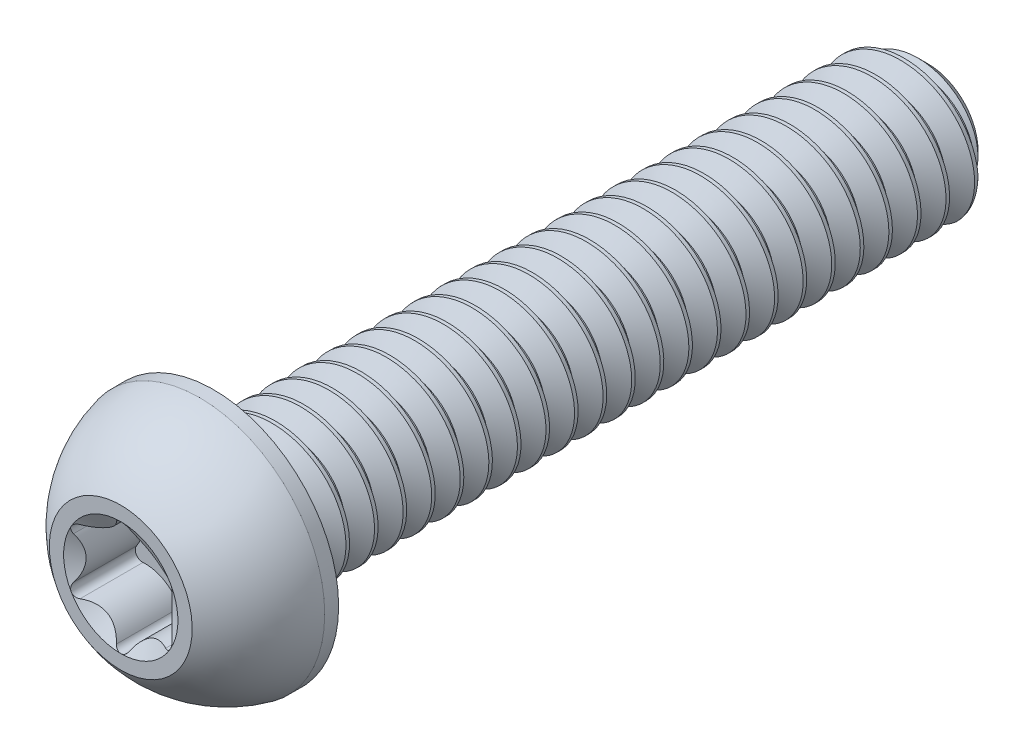
SolidWorks part; units mm, degrees
material "18-8 Stainless Steel"
ref_plane "Front" through (0, 0, 0) normal (0, 0, 1) x (1, 0, 0)
ref_plane "Top" through (0, 0, 0) normal (0, 1, 0) x (1, 0, 0)
ref_plane "Right" through (0, 0, 0) normal (1, 0, 0) x (0, 0, -1)
sketch "Sketch1" plane through (0, 0, 0) normal (1, 0, 0) x (0, 0, -1)
  line L2 (1.3, 1) -> (11.3, 1)
  line L3 (11.3, 1) -> (11.3, 0)
  line L4 (11.3, 0) -> (1.3, 0)
  line L6 (1.105, 1.75) -> (1.3, 1.75) construction
  line L7 (11.3, 1) -> (11.3, -1) construction
  line L8 (0, 0) -> (1.3, 0) construction
  line L9 (1.3, 1.75) -> (1.3, -1.75) construction
  line L11 (1.3, 1) -> (1.3, 0)
  line L14 (0, 0) -> (0, 1) construction
  arc A3 (0, 1) -> (1.105, 1.75) centre (1.4858, 0) cw construction
  dimension "D1" = 0.195
revolve "Revolve1" add sketch "Sketch1" angle 360 mid plane about L4
sketch "Sketch3" plane through (0, 0, -11.3) normal (0, 0, -1) x (-1, 0, 0)
  circle A0 centre (0, 0) radius 1
curve "Helix/Spiral1" pitch 0.4 height 10.4 radius 1 centre (0, 0, -11.3) axis (0, 0, 1) start towards (0, 1, 0)
sketch "Sketch2" plane through (0, 0, 0) normal (1, 0, 0) x (0, 0, -1)
  line L0 (11.3, 1) -> (11.65, 1) construction
  line L1 (11.65, 1) -> (11.5, 0.7402)
  line L2 (11.5, 0.7402) -> (11.45, 0.7402)
  line L3 (11.45, 0.7402) -> (11.3, 1)
  line L4 (11.375, 0.8701) -> (11.575, 0.8701) construction
  line L5 (11.3, 1) -> (11.2423, 1.1)
  line L6 (11.2423, 1.1) -> (11.7077, 1.1)
  line L7 (11.7077, 1.1) -> (11.65, 1)
  dimension "D1" = 60
  dimension "D2" = 0.05
  dimension "D3" = 0.2
  dimension "D4" = 0.1
chamfer "Chamfer1" distance 0.3 angle 45 1 edges at (0, 1, -11.3)
sweep "Cut-Sweep1" cut profiles "Sketch2" path "Helix/Spiral1" align with end faces yes
sketch "Sketch7" plane through (0, 0, 0) normal (1, 0, 0) x (0, 0, -1)
  line L0 (0, 0) -> (0, 1) construction
  line L6 (1.105, 1.75) -> (1.3, 1.75) construction
  line L8 (0, 0) -> (1.3, 0) construction
  line L11 (1.3, 1.75) -> (1.3, -1.75) construction
  line L12 (1.105, 1.75) -> (1.3, 1.75)
  line L13 (0, 0) -> (1.3, 0)
  line L15 (1.3, 1.75) -> (1.3, 0)
  line L16 (0, 1) -> (0, 0)
  arc A2 (1.105, 1.75) -> (0, 1) centre (1.4858, 0) ccw construction
  arc A3 (1.105, 1.75) -> (0, 1) centre (1.4858, 0) ccw
revolve "Revolve2" add sketch "Sketch7" angle 360 mid plane about L13
sketch "Sketch5" plane through (0, 0, 0) normal (0, 0, 1) x (1, 0, 0)
  line L0 (4.18, 0) -> (-4.18, 0) construction
  line L2 (0, 0) -> (-0.6928, 0.4)
  line L3 (0, 0) -> (-0.6928, -0.4)
  line L4 (0, 0.8) -> (0, 0.7) construction
  line L5 (0, 0.7) -> (0, 0.6) construction
  circle A0 centre (0, 0) radius 0.6 construction
  circle A1 centre (0, 0) radius 0.7 construction
  circle A2 centre (0, 0) radius 0.8 construction
  arc A3 (-0.6894, 0.2944) -> (-0.6894, -0.2944) centre (-1.1298, 0) cw
  arc A4 (-0.6894, 0.2944) -> (-0.6928, 0.4) centre (-0.6062, 0.35) cw
  arc A5 (-0.6894, -0.2944) -> (-0.6928, -0.4) centre (-0.6062, -0.35) ccw
  dimension "D4" = 1.2
  dimension "D2" = 1.6
  dimension "D1" = 30
extrude "Cut-Extrude2" cut sketch "Sketch5" against normal blind 0.91
pattern_circular "CirPattern1" count 6 over 360 of "Cut-Extrude2"
sketch "Sketch11" plane through (0, 0, 0) normal (0, 0, 1) x (1, 0, 0)
  circle A0 centre (0, 0) radius 0.8 construction
  circle A1 centre (0, 0) radius 0.8
extrude "Cut-Extrude3" cut sketch "Sketch11" against normal blind 0.91 draft 60
sketch "Sketch9" [suppressed] plane through (0, 0, -1.4986) normal (0, 0, 1) x (1, 0, 0)
  circle A2 centre (0, 0) radius 1.4224
extrude "Boss-Extrude2" [suppressed] add sketch "Sketch9" against normal offset from surface (7.0104 mm away) 31.75 up to face at (0, 0.7, -11.3)
sketch "Sketch10" plane through (0, 0, 0) normal (1, 0, 0) x (0, 0, -1)
  line L0 (11.3, 1) -> (11.3, -1) construction
  point P0 (10.7, -1)
  dimension "D1" = 0.6
equation "\"D3@Helix/Spiral1\" = \"Lg@Sketch1\" + \"D4@Helix/Spiral1\""
equation "\"D2@Sketch2\" = \"D4@Helix/Spiral1\" * .125"
equation "\"D3@Sketch2\" = \"D4@Helix/Spiral1\" * .5"
equation "\"D1@Chamfer1\" = \"D4@Helix/Spiral1\" * .75"
equation "\"D1@Cut-Extrude2\" = \"Head Ht@Sketch1\" * .7"
equation "\"D1@Sketch1\" = \"Head Ht@Sketch1\" * .15"
equation "\"D1@Sketch10\" = \"D4@Helix/Spiral1\" * 1.5"
equation "\"D1@Cut-Extrude3\" = \"D1@Cut-Extrude2\""
equation "\"D2@Sketch5\" = \"Dia@Sketch1\" * .8"
equation "\"D4@Sketch5\" = \"D2@Sketch5\" * .75"
